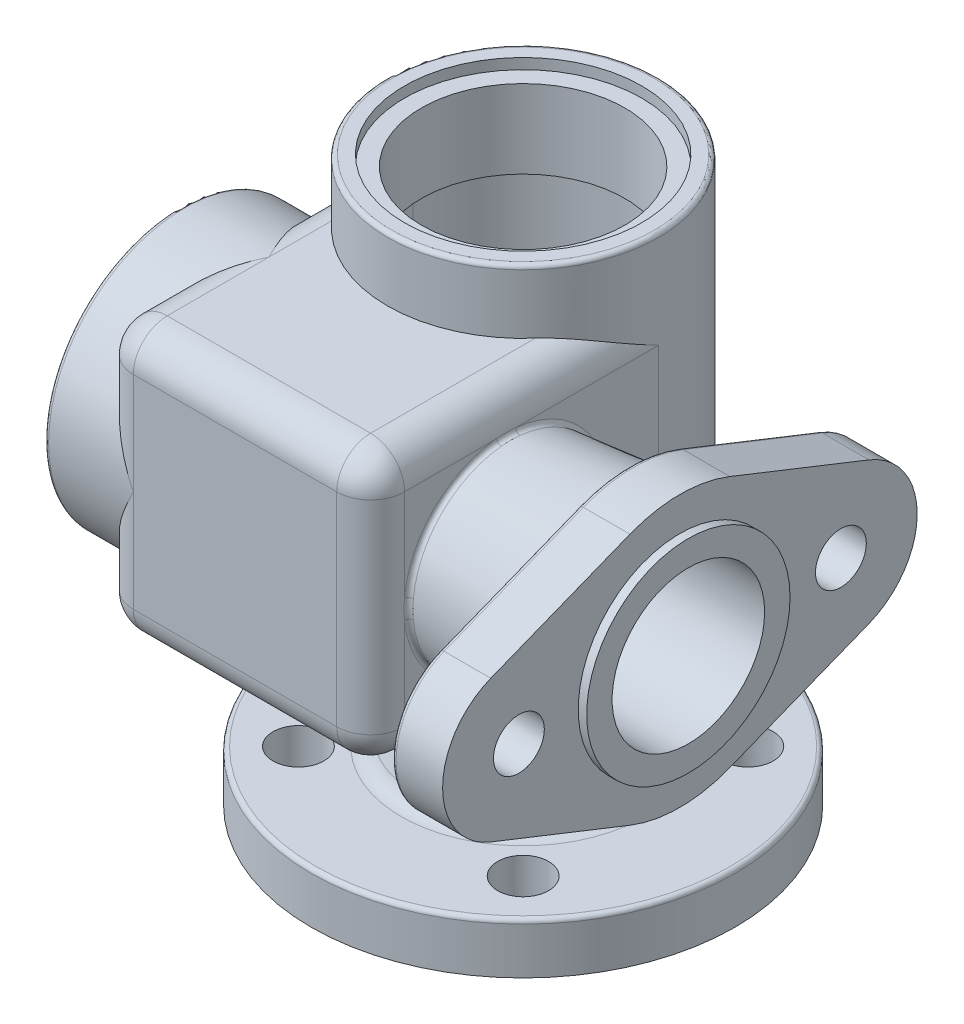
SolidWorks part; units mm, degrees
ref_plane "前基準面" through (0, 0, 0) normal (0, 0, 1) x (1, 0, 0)
ref_plane "上基準面" through (0, 0, 0) normal (0, 1, 0) x (1, 0, 0)
ref_plane "右基準面" through (0, 0, 0) normal (1, 0, 0) x (0, 0, -1)
sketch "草圖1" plane through (0, 0, 0) normal (0, 0, 1) x (1, 0, 0)
  line L0 (0, 0) -> (30, 0)
  line L1 (30, 0) -> (30, 2)
  line L2 (30, 2) -> (50, 2)
  line L3 (50, 2) -> (50, 13)
  line L4 (49, 14) -> (28.772, 14)
  line L5 (25.0267, 16.5955) -> (20.9737, 27.4035)
  line L6 (32, 54.98) -> (32, 134)
  line L7 (31, 135) -> (0, 135)
  line L8 (0, 0) -> (0, 162.4144) construction
  line L9 (0, 0) -> (0, 135)
  arc A0 (21.9724, 31.716) -> (32, 54.98) centre (0, 54.98) ccw
  arc A1 (20.9737, 27.4035) -> (21.9724, 31.716) centre (24.719, 28.808) cw
  arc A2 (32, 134) -> (31, 135) centre (31, 134) ccw
  arc A3 (50, 13) -> (49, 14) centre (49, 13) ccw
  arc A4 (28.772, 14) -> (25.0267, 16.5955) centre (28.772, 18) cw
  point P15 (20, 30)
  point P18 (32, 135)
  point P21 (50, 14)
  point P24 (26, 14)
  dimension "D8" = 32
  dimension "D11" = 4
  dimension "D12" = 1
  dimension "D13" = 4
  dimension "D1" = 32
  dimension "D2" = 30
  dimension "D3" = 2
  dimension "D4" = 50
  dimension "D5" = 20
  dimension "D6" = 28
  dimension "D7" = 26
  dimension "D9" = 133
  dimension "D10" = 12
revolve "旋轉1" add sketch "草圖1" angle 360 about L8
ref_plane "平面1" through (0, 0, 36) normal (0, 0, 1) x (1, 0, 0)
sketch "草圖2" plane through (0, 0, 36) normal (0, 0, 1) x (1, 0, 0)
  line L0 (32, 54.98) -> (32, 134) construction
  line L1 (-32, 56) -> (32, 56)
  line L2 (-32, 56) -> (-32, 120)
  line L3 (-32, 120) -> (32, 120)
  line L4 (32, 56) -> (32, 120)
  line L5 (-32, 134) -> (-32, 54.98) construction
  line L6 (-32, 88) -> (37.439, 88) construction
  line L7 (-50, 2) -> (50, 2) construction
  dimension "D1" = 64
  dimension "D2" = 86
extrude "填料-伸長1" add sketch "草圖2" against normal up to next and the other way blind 32
fillet "圓角1" radius 8 4 edges at (-32, 56, 34) (32, 56, 34) (32, 120, 34) (-32, 120, 34)
fillet "圓角2" radius 8 8 edges at (-29.6569, 117.6569, 68) (0, 120, 68) (29.6569, 117.6569, 68) (32, 88, 68) (29.6569, 58.3431, 68) (0, 56, 68) (-29.6569, 58.3431, 68) (-32, 88, 68)
sketch "草圖3" plane through (32, 0, 0) normal (1, 0, 0) x (0, 0, -1)
  line L0 (0, 112) -> (0, 64) construction
  line L1 (-68, 88) -> (8.6002, 88) construction
  line L2 (-68, 64) -> (-68, 112) construction
  circle A0 centre (-36, 88) radius 23
  dimension "D1" = 46
  dimension "D2" = 36
ref_plane "平面2" through (61, 0, 0) normal (1, 0, 0) x (0, 0, -1)
sketch "草圖4" plane through (61, 0, 0) normal (1, 0, 0) x (0, 0, -1)
  circle A0 centre (-36, 88) radius 26
  dimension "D1" = 52
loft "疊層拉伸1" add profiles "草圖4", "草圖3" connector at (61, 111.3085, 47.5201) connector at (32, 106.5819, 49.5541)
sketch "草圖5" plane through (61, 0, 0) normal (1, 0, 0) x (0, 0, -1)
  line L0 (-36, 88) -> (-74, 88) construction
  line L1 (-80.6316, 104.7339) -> (-47.7895, 117.7491)
  line L2 (-80.6316, 71.2661) -> (-47.7895, 58.2509)
  line L3 (-36, 88) -> (-36, 78.8383) construction
  line L4 (8.6316, 104.7339) -> (-24.2105, 117.7491)
  line L5 (8.6316, 71.2661) -> (-24.2105, 58.2509)
  arc A0 (-47.7895, 58.2509) -> (-24.2105, 58.2509) centre (-36, 88) ccw
  arc A1 (-80.6316, 104.7339) -> (-80.6316, 71.2661) centre (-74, 88) ccw
  arc A2 (8.6316, 104.7339) -> (8.6316, 71.2661) centre (2, 88) cw
  arc A3 (-24.2105, 117.7491) -> (-47.7895, 117.7491) centre (-36, 88) ccw
  dimension "D1" = 64
  dimension "D2" = 36
  dimension "D3" = 38
extrude "填料-伸長2" add sketch "草圖5" along normal blind 12
sketch "草圖6" plane through (73, 0, 0) normal (1, 0, 0) x (0, 0, -1)
  circle A0 centre (-36, 88) radius 24
  dimension "D1" = 48
extrude "填料-伸長3" add sketch "草圖6" along normal blind 2
sketch "草圖7" plane through (73, 0, 0) normal (1, 0, 0) x (0, 0, -1)
  line L0 (-36, 88) -> (-36, 77.9752) construction
  line L1 (-36, 88) -> (12.0831, 88) construction
  line L2 (-36, 88) -> (-83.5033, 88) construction
  circle A0 centre (-74, 88) radius 6
  circle A1 centre (2, 88) radius 6
  dimension "D1" = 12
  dimension "D2" = 76
extrude "除料-伸長1" cut sketch "草圖7" against normal up to next
sketch "草圖8" plane through (75, 0, 0) normal (1, 0, 0) x (0, 0, -1)
  circle A0 centre (-36, 88) radius 18
  dimension "D1" = 36
extrude "除料-伸長2" cut sketch "草圖8" against normal blind 53
ref_plane "平面3" through (0, 62, 0) normal (0, 1, 0) x (1, 0, 0)
sketch "草圖9" plane through (0, 62, 0) normal (0, 1, 0) x (1, 0, 0)
  line L1 (26, 0) -> (26, -62)
  line L2 (26, -62) -> (-26, -62)
  line L3 (-26, -62) -> (-26, 0)
  line L4 (-24, -68) -> (24, -68) construction
  arc A0 (26, 0) -> (-26, 0) centre (0, 0) ccw
  dimension "D1" = 52
  dimension "D2" = 6
extrude "除料-伸長3" cut sketch "草圖9" along normal blind 52
sketch "草圖10" plane through (0, 135, 0) normal (0, 1, 0) x (1, 0, 0)
  circle A0 centre (0, 0) radius 28
  dimension "D1" = 56
extrude "除料-伸長4" cut sketch "草圖10" against normal blind 2.5
sketch "草圖11" plane through (0, 132.5, 0) normal (0, 1, 0) x (1, 0, 0)
  circle A0 centre (0, 0) radius 24
  dimension "D1" = 48
extrude "除料-伸長5" cut sketch "草圖11" against normal up to next
sketch "草圖12" plane through (0, 0, 0) normal (0, -1, 0) x (1, 0, 0)
  circle A0 centre (0, 0) radius 12.5
  dimension "D1" = 25
extrude "除料-伸長6" cut sketch "草圖12" against normal blind 39
sketch "草圖13" plane through (0, 39, 0) normal (0, -1, 0) x (1, 0, 0)
  circle A0 centre (0, 0) radius 18
  dimension "D1" = 36
extrude "除料-伸長7" cut sketch "草圖13" against normal blind 10
ref_plane "平面4" through (-45, 0, 0) normal (1, 0, 0) x (0, 0, -1)
sketch "草圖15" plane through (-45, 0, 0) normal (1, 0, 0) x (0, 0, -1)
  line L0 (-74, 88) -> (-12.388, 88) construction
  circle A0 centre (-36, 88) radius 32
  circle A2 centre (-36, 88) radius 24
  circle A3 centre (-36, 88) radius 24 construction
  dimension "D1" = 64
  dimension "D2" = 0
extrude "填料-伸長4" add sketch "草圖15" along normal up to next
sketch "草圖16" plane through (-45, 0, 0) normal (-1, 0, 0) x (0, 0, 1)
  circle A0 centre (36, 88) radius 24
  dimension "D1" = 48
extrude "除料-伸長8" cut sketch "草圖16" against normal blind 4
sketch "草圖17" plane through (-41, 0, 0) normal (-1, 0, 0) x (0, 0, 1)
  circle A0 centre (36, 88) radius 19.5
  dimension "D1" = 39
extrude "除料-伸長9" cut sketch "草圖17" against normal up to next
sketch "草圖18" plane through (0, 14, 0) normal (0, 1, 0) x (1, 0, 0)
  line L0 (0, 0) -> (14.2872, 0) construction
  line L1 (0, 0) -> (44.8716, 44.8716) construction
  circle A0 centre (0, 0) radius 37.5 construction
  circle A1 centre (26.5165, 26.5165) radius 6
  dimension "D1" = 75
  dimension "D3" = 12
  dimension "D2" = 45
extrude "除料-伸長10" cut sketch "草圖18" against normal through all
ref_axis "基準軸1" through (0, -6.75, 0) along (0, 1, 0)
pattern_circular "環狀複製排列1" count 4 over 360 about axis through (0, -6.75, 0) along (0, 1, 0) of "除料-伸長10"
fillet "圓角3" radius 1 8 edges at (61, 120, 36) (61, 111.2415, 7.7895) (61, 88, -20) (61, 64.7585, 7.7895) (61, 56, 36) (61, 64.7585, 64.2105) (61, 88, 92) (61, 111.2415, 64.2105)
fillet "圓角4" radius 1 3 edges at (-45, 88, 4) (32, 88, 13) (61, 88, 10)
sketch "草圖19" plane through (0, 62, 0) normal (0, 1, 0) x (1, 0, 0)
  circle A0 centre (0, 0) radius 16.5
  dimension "D1" = 33
extrude "除料-伸長11" cut sketch "草圖19" against normal up to next
